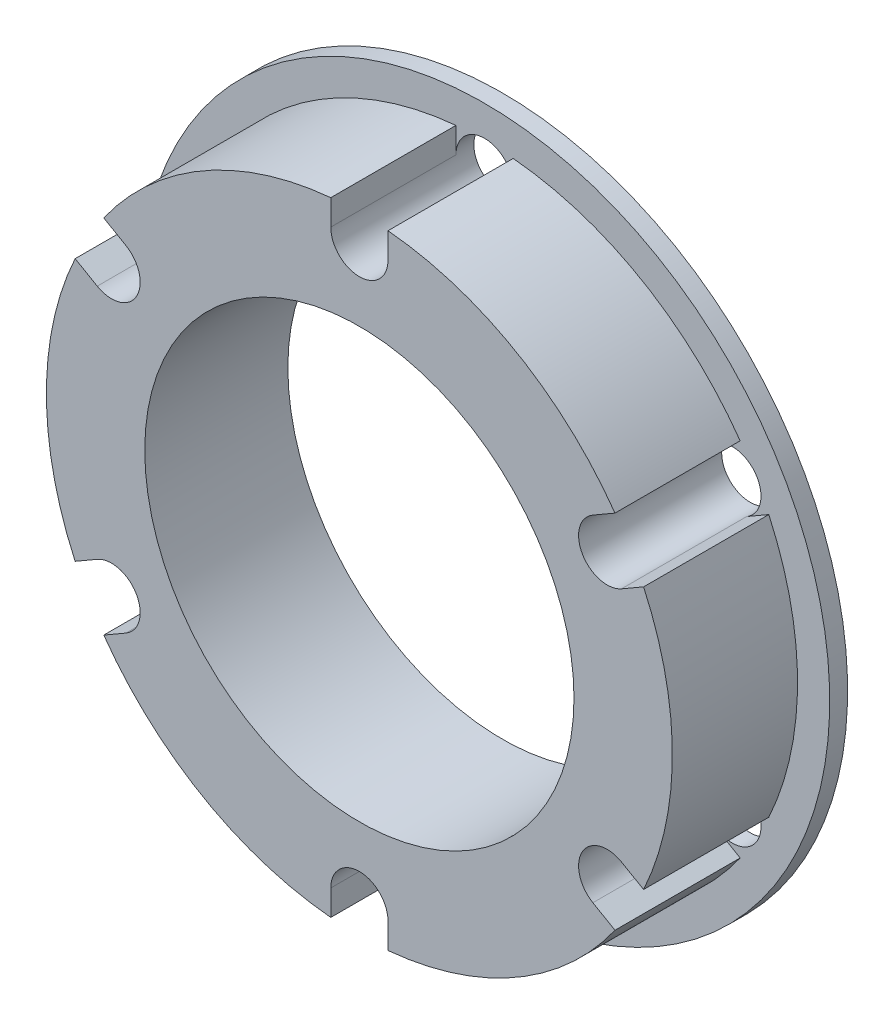
SolidWorks part; units mm, degrees
material "7075-O (SS)"
ref_plane "Front" through (0, 0, 0) normal (0, 0, 1) x (1, 0, 0)
ref_plane "Top" through (0, 0, 0) normal (0, 1, 0) x (1, 0, 0)
ref_plane "Right" through (0, 0, 0) normal (1, 0, 0) x (0, 0, -1)
sketch "Croquis1" plane through (0, 0, 0) normal (0, 1, 0) x (1, 0, 0)
  line L0 (-12, 4.5) -> (-19.3, 4.5)
  line L1 (-19.3, 4.5) -> (-19.3, 3.5)
  line L2 (-19.3, 3.5) -> (-17.5, 3.5)
  line L3 (-17.5, 3.5) -> (-17.5, -3.5)
  line L4 (-17.5, -3.5) -> (-12, -3.5)
  line L5 (-12, -3.5) -> (-12, 4.5)
  line L6 (0, -55) -> (0, 55) construction
  line L7 (-55, 0) -> (55, 0) construction
  line L8 (0, 14.9098) -> (0, -20.3901) construction
  point P8 (-17.5, 0)
  dimension "D1" = 12
  dimension "D2" = 7
  dimension "D3" = 1
  dimension "D4" = 17.5
  dimension "D5" = 19.3
revolve "Revolución1" add sketch "Croquis1" angle 360 about L8
sketch "Croquis2" plane through (0, 0, 3.5) normal (0, 0, 1) x (1, 0, 0)
  line L0 (0, -4.4) -> (0, 4.4) construction
  line L1 (1.6, 16) -> (1.6, 17.4267)
  line L2 (-1.6, 16) -> (-1.6, 17.4267)
  line L3 (4.4, 0) -> (-4.4, 0) construction
  line L4 (14.6564, 6.6144) -> (15.892, 7.3277)
  line L5 (13.0564, 9.3856) -> (14.292, 10.099)
  line L6 (13.0564, -9.3856) -> (14.292, -10.099)
  line L7 (14.6564, -6.6144) -> (15.892, -7.3277)
  line L8 (-1.6, -16) -> (-1.6, -17.4267)
  line L9 (1.6, -16) -> (1.6, -17.4267)
  line L10 (-14.6564, -6.6144) -> (-15.892, -7.3277)
  line L11 (-13.0564, -9.3856) -> (-14.292, -10.099)
  line L12 (-13.0564, 9.3856) -> (-14.292, 10.099)
  line L13 (-14.6564, 6.6144) -> (-15.892, 7.3277)
  circle A1 centre (0, 0) radius 17.5 construction
  circle A2 centre (0, 0) radius 17.5 construction
  arc A3 (1.6, 17.4267) -> (-1.6, 17.4267) centre (0, 0) ccw
  arc A4 (-1.6, 16) -> (1.6, 16) centre (0, 16) ccw
  arc A5 (15.892, 7.3277) -> (14.292, 10.099) centre (0, 0) ccw
  arc A6 (13.0564, 9.3856) -> (14.6564, 6.6144) centre (13.8564, 8) ccw
  arc A7 (14.292, -10.099) -> (15.892, -7.3277) centre (0, 0) ccw
  arc A8 (14.6564, -6.6144) -> (13.0564, -9.3856) centre (13.8564, -8) ccw
  arc A9 (-1.6, -17.4267) -> (1.6, -17.4267) centre (0, 0) ccw
  arc A10 (1.6, -16) -> (-1.6, -16) centre (0, -16) ccw
  arc A11 (-15.892, -7.3277) -> (-14.292, -10.099) centre (0, 0) ccw
  arc A12 (-13.0564, -9.3856) -> (-14.6564, -6.6144) centre (-13.8564, -8) ccw
  arc A13 (-14.292, 10.099) -> (-15.892, 7.3277) centre (0, 0) ccw
  arc A14 (-14.6564, 6.6144) -> (-13.0564, 9.3856) centre (-13.8564, 8) ccw
  dimension "D1" = 1.6
  dimension "D2" = 16
  dimension "D3" = 6
extrude "Cortar-Extruir1" cut sketch "Croquis2" against normal up to surface (7 mm away) up to face at (-17.5, 0, -3.5)
sketch "Croquis5" plane through (0, 0, -4.5) normal (0, 0, -1) x (-1, 0, 0)
  line L0 (0, 4.4) -> (0, -4.4) construction
  line L1 (4.4, 0) -> (-4.4, 0) construction
  circle A0 centre (0, 16) radius 1.6
  circle A1 centre (13.8564, 8) radius 1.6
  circle A2 centre (13.8564, -8) radius 1.6
  circle A3 centre (0, -16) radius 1.6
  circle A4 centre (-13.8564, -8) radius 1.6
  circle A5 centre (-13.8564, 8) radius 1.6
  dimension "D1" = 3.2
  dimension "D2" = 16
  dimension "D3" = 6
extrude "Cortar-Extruir2" cut sketch "Croquis5" against normal up to next
